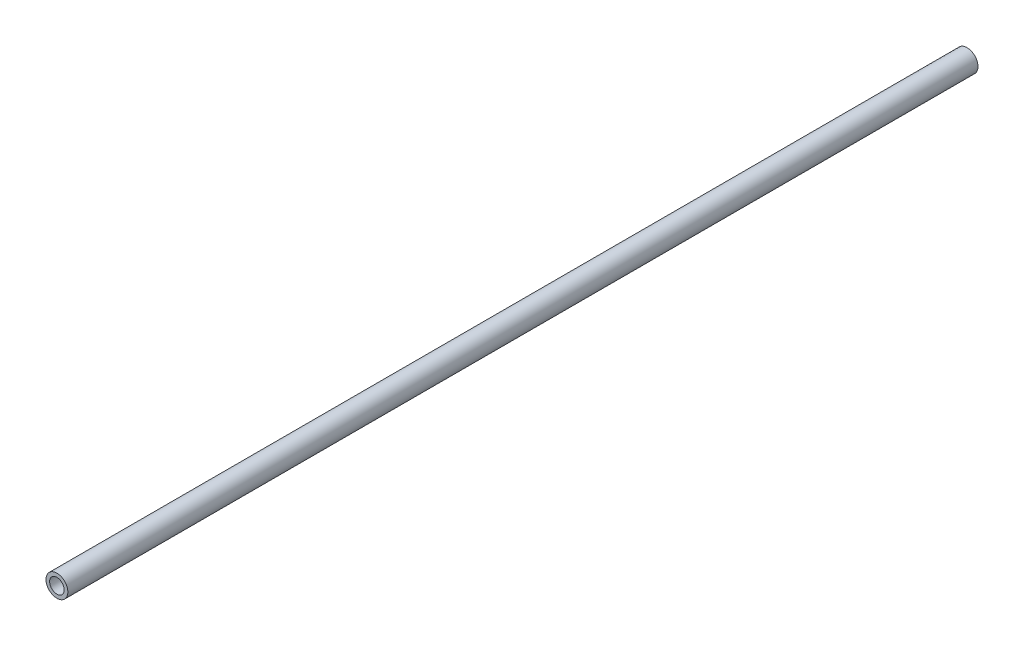
SolidWorks part; units mm, degrees
ref_plane "Front Plane" through (0, 0, 0) normal (0, 0, 1) x (1, 0, 0)
ref_plane "Top Plane" through (0, 0, 0) normal (0, 1, 0) x (1, 0, 0)
ref_plane "Right Plane" through (0, 0, 0) normal (1, 0, 0) x (0, 0, -1)
sketch "Sketch1" plane through (0, 0, 0) normal (0, 0, 1) x (1, 0, 0)
  circle A0 centre (0, 0) radius 6
  dimension "D1" = 12
extrude "Extrude-Thin1" add sketch "Sketch1" along normal mid plane 500 thin thin type one direction reverse wall 2
